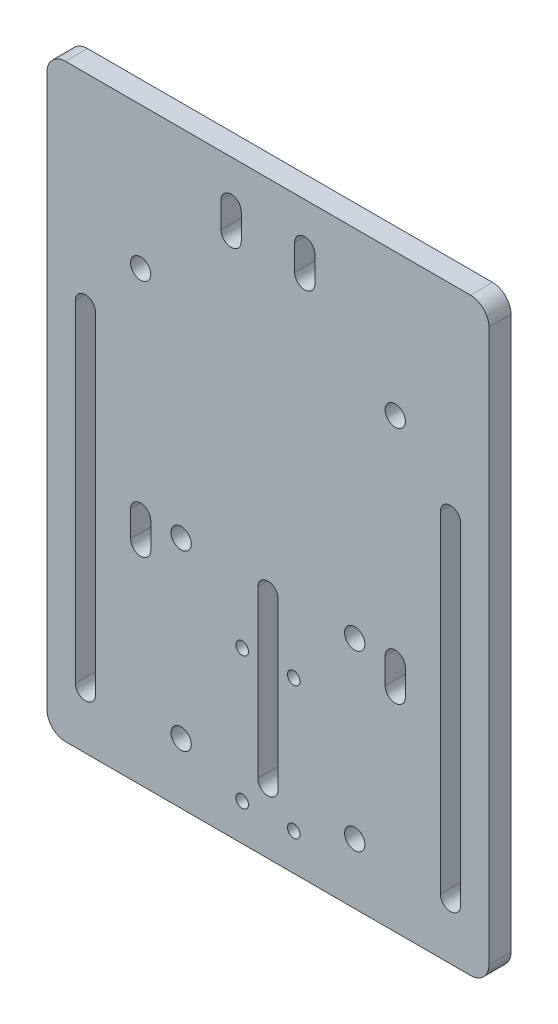
SolidWorks part; units mm, degrees
material "PET"
ref_plane "Front Plane" through (0, 0, 0) normal (0, 0, 1) x (1, 0, 0)
ref_plane "Top Plane" through (0, 0, 0) normal (0, 1, 0) x (1, 0, 0)
ref_plane "Right Plane" through (0, 0, 0) normal (1, 0, 0) x (0, 0, -1)
sketch "Sketch2" plane through (0, 0, 0) normal (0, 0, 1) x (1, 0, 0)
  line L1 (-55, -80) -> (55, -80)
  line L2 (-60, -75) -> (-60, 75)
  line L3 (-55, 80) -> (55, 80)
  line L4 (60, -75) -> (60, 75)
  line L5 (-60, -80) -> (60, 80) construction
  line L6 (-60, 80) -> (60, -80) construction
  arc A0 (55, -80) -> (60, -75) centre (55, -75) ccw
  arc A1 (-55, -80) -> (-60, -75) centre (-55, -75) cw
  arc A2 (55, 80) -> (60, 75) centre (55, 75) cw
  arc A3 (-60, 75) -> (-55, 80) centre (-55, 75) cw
  point P0 (0, 0)
  dimension "D3" = 5
  dimension "D1" = 120
  dimension "D2" = 160
extrude "Boss-Extrude1" add sketch "Sketch2" along normal blind 6
sketch "Sketch3" plane through (0, 0, 6) normal (0, 0, 1) x (1, 0, 0)
  line L0 (0, -17.5) -> (0, -62.5) construction
  line L1 (2.75, -17.5) -> (2.75, -62.5)
  line L2 (-2.75, -17.5) -> (-2.75, -62.5)
  line L3 (-55, -80) -> (55, -80) construction
  arc A0 (2.75, -17.5) -> (-2.75, -17.5) centre (0, -17.5) ccw
  arc A1 (-2.75, -62.5) -> (2.75, -62.5) centre (0, -62.5) ccw
  point P3 (0, -40)
  dimension "D1" = 2.75
  dimension "D2" = 45
  dimension "D3" = 40
extrude "Cut-Extrude1" cut sketch "Sketch3" against normal blind 6
hole_wizard "M5 Clearance Hole1" positions "Sketch4" profile "Sketch5" hole size "M5" standard "ANSI Metric" end condition through all
sketch "Sketch4" plane through (0, 0, 6) normal (0, 0, 1) x (1, 0, 0)
  point P0 (-23.57, -63.57)
  point P2 (-23.57, -16.43)
  point P4 (23.57, -16.43)
  point P6 (23.57, -63.57)
  dimension "D1" = 23.57
  dimension "D2" = 23.57
  dimension "D3" = 23.57
  dimension "D4" = 47.14
sketch "Sketch5" plane through (-23.57, -63.57, 6) normal (1, 0, 0) x (0, -1, 0)
  line L0 (0, 0) -> (0, 6)
  line L1 (0, 6) -> (2.75, 6)
  line L2 (2.75, 6) -> (2.75, 0)
  line L5 (2.75, 0) -> (0, 0)
  line L11 (0, -6.35) -> (0, 107.95) construction
  dimension "Thru Hole Dia." = 5.5
  dimension "Thru Hole Depth" = 6
sketch "Sketch6" plane through (0, 0, 6) normal (0, 0, 1) x (1, 0, 0)
  line L0 (-34.57, -16.43) -> (-34.57, -23.43) construction
  line L1 (-31.82, -16.43) -> (-31.82, -23.43)
  line L2 (-37.32, -16.43) -> (-37.32, -23.43)
  arc A0 (-31.82, -16.43) -> (-37.32, -16.43) centre (-34.57, -16.43) ccw
  arc A1 (-37.32, -23.43) -> (-31.82, -23.43) centre (-34.57, -23.43) ccw
  point P2 (-34.57, -19.93)
  dimension "D1" = 2.75
  dimension "D2" = 7
  dimension "D3" = 11
extrude "Cut-Extrude2" cut sketch "Sketch6" against normal blind 22
hole_wizard "M5 Clearance Hole2" positions "Sketch7" profile "Sketch8" hole size "M5" standard "ANSI Metric" end condition through all
sketch "Sketch7" plane through (0, 0, 6) normal (0, 0, 1) x (1, 0, 0)
  point P0 (-34.57, 41.47)
  dimension "D1" = 61.4
sketch "Sketch8" plane through (-34.57, 41.47, 6) normal (1, 0, 0) x (0, -1, 0)
  line L0 (0, 0) -> (0, 6)
  line L1 (0, 6) -> (2.75, 6)
  line L2 (2.75, 6) -> (2.75, 0)
  line L5 (2.75, 0) -> (0, 0)
  line L11 (0, -6.35) -> (0, 107.95) construction
  dimension "Thru Hole Dia." = 5.5
  dimension "Thru Hole Depth" = 6
sketch "Sketch9" plane through (0, 0, 6) normal (0, 0, 1) x (1, 0, 0)
  line L0 (-49.57, 25.07) -> (-49.57, -64.93) construction
  line L1 (-46.82, 25.07) -> (-46.82, -64.93)
  line L2 (-52.32, 25.07) -> (-52.32, -64.93)
  arc A0 (-46.82, 25.07) -> (-52.32, 25.07) centre (-49.57, 25.07) ccw
  arc A1 (-52.32, -64.93) -> (-46.82, -64.93) centre (-49.57, -64.93) ccw
  point P2 (-49.57, -19.93)
  dimension "D2" = 2.75
  dimension "D1" = 15
  dimension "D3" = 90
extrude "Cut-Extrude3" cut sketch "Sketch9" against normal blind 6
sketch "Sketch10" plane through (0, 0, 6) normal (0, 0, 1) x (1, 0, 0)
  line L0 (0, 85.855) -> (0, -97.3195) construction
mirror "Mirror2" about plane through (0, 0, 0) normal (1, 0, 0) of "M5 Clearance Hole2", "Cut-Extrude3", "Cut-Extrude2"
sketch "Sketch11" plane through (0, 0, 6) normal (0, 0, 1) x (1, 0, 0)
  line L0 (-10, 68.5) -> (-10, 61.5) construction
  line L1 (-7.25, 68.5) -> (-7.25, 61.5)
  line L2 (-12.75, 68.5) -> (-12.75, 61.5)
  line L3 (10, 68.5) -> (10, 61.5) construction
  line L4 (12.75, 68.5) -> (12.75, 61.5)
  line L5 (7.25, 68.5) -> (7.25, 61.5)
  line L9 (55, 80) -> (-55, 80) construction
  arc A0 (-7.25, 68.5) -> (-12.75, 68.5) centre (-10, 68.5) ccw
  arc A1 (-12.75, 61.5) -> (-7.25, 61.5) centre (-10, 61.5) ccw
  arc A2 (12.75, 68.5) -> (7.25, 68.5) centre (10, 68.5) ccw
  arc A3 (7.25, 61.5) -> (12.75, 61.5) centre (10, 61.5) ccw
  point P2 (-10, 65)
  point P7 (10, 65)
  dimension "D1" = 2.75
  dimension "D4" = 10
  dimension "D2" = 7
  dimension "D3" = 20
  dimension "D5" = 15
extrude "Cut-Extrude4" cut sketch "Sketch11" against normal blind 6
hole_wizard "M3 Clearance Hole1" positions "Sketch12" profile "Sketch13" hole size "M3" standard "ANSI Metric"
sketch "Sketch12" plane through (0, 0, 6) normal (0, 0, 1) x (1, 0, 0)
  line L0 (0, 85.855) -> (0, -97.3195) construction
  line L1 (-55, -80) -> (55, -80) construction
  point P0 (-7, -34)
  point P2 (7, -34)
  point P4 (7, -70)
  point P6 (-7, -70)
  dimension "D1" = 7
  dimension "D2" = 14
  dimension "D3" = 36
  dimension "D4" = 10
sketch "Sketch13" plane through (-7, -34, 6) normal (1, 0, 0) x (0, -1, 0)
  line L0 (0, 0) -> (0, 11.0215)
  line L1 (0, 11.0215) -> (1.7, 10)
  line L2 (1.7, 10) -> (1.7, 0)
  line L5 (1.7, 0) -> (0, 0)
  line L10 (0, 11.0215) -> (-1.7, 10) construction
  line L11 (0, -6.35) -> (0, 107.95) construction
  dimension "Hole Dia." = 3.4
  dimension "Hole Depth" = 10
  dimension "Drill Angle" = 118
